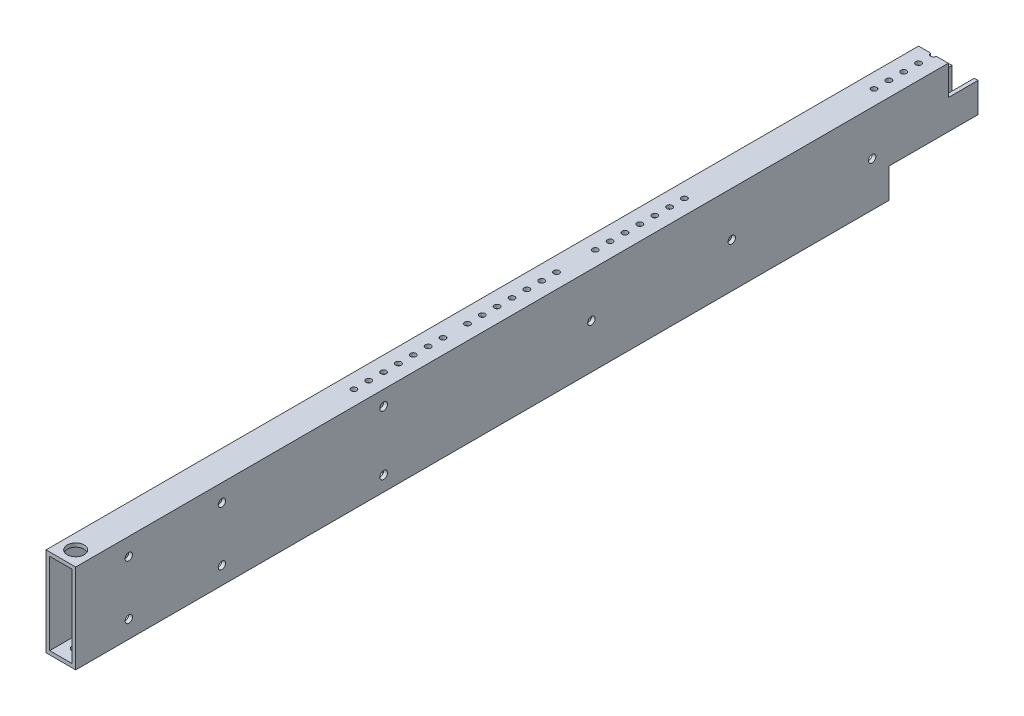
SolidWorks part; units mm, degrees
ref_plane "Front Plane" through (0, 0, 0) normal (0, 0, 1) x (1, 0, 0)
ref_plane "Top Plane" through (0, 0, 0) normal (0, 1, 0) x (1, 0, 0)
ref_plane "Right Plane" through (0, 0, 0) normal (1, 0, 0) x (0, 0, -1)
sketch "Sketch1" plane through (0, 0, 0) normal (0, 0, 1) x (1, 0, 0)
  line L1 (-12.7, -38.1) -> (12.7, -38.1)
  line L2 (-12.7, -38.1) -> (-12.7, 38.1)
  line L3 (-12.7, 38.1) -> (12.7, 38.1)
  line L4 (12.7, -38.1) -> (12.7, 38.1)
  line L5 (-12.7, -38.1) -> (12.7, 38.1) construction
  line L6 (-12.7, 38.1) -> (12.7, -38.1) construction
  point P0 (0, 0)
  dimension "D1" = 25.4
  dimension "D2" = 76.2
extrude "Boss-Extrude1" add sketch "Sketch1" along normal mid plane 771.398
shell "Shell1" thickness 3.175 removed face at (0, 0, -385.699) removed face at (0, 0, 385.699)
sketch "Sketch2" plane through (12.7, 0, 0) normal (1, 0, 0) x (0, 0, -1)
  line L1 (385.699, -38.1) -> (309.499, -38.1)
  line L2 (385.699, -38.1) -> (385.699, -12.7)
  line L3 (385.699, -12.7) -> (309.499, -12.7)
  line L4 (309.499, -38.1) -> (309.499, -12.7)
  dimension "D1" = 25.4
  dimension "D2" = 76.2
extrude "Cut-Extrude1" cut sketch "Sketch2" against normal through all
sketch "Sketch3" plane through (12.7, 0, 0) normal (1, 0, 0) x (0, 0, -1)
  line L1 (385.699, 38.1) -> (360.299, 38.1)
  line L2 (385.699, 38.1) -> (385.699, 12.7)
  line L3 (385.699, 12.7) -> (360.299, 12.7)
  line L4 (360.299, 38.1) -> (360.299, 12.7)
  dimension "D1" = 25.4
extrude "Cut-Extrude2" cut sketch "Sketch3" against normal through all
sketch "Sketch4" plane through (0, 38.1, 0) normal (0, 1, 0) x (1, 0, 0)
  line L0 (-12.7, 360.299) -> (12.7, 360.299) construction
  circle A0 centre (0, 147.3945) radius 2.3812
  circle A1 centre (0, 134.6945) radius 2.3812
  circle A2 centre (0, 121.9945) radius 2.3812
  circle A3 centre (0, 109.2945) radius 2.3812
  circle A4 centre (0, 96.5945) radius 2.3812
  circle A5 centre (0, 83.8945) radius 2.3812
  circle A6 centre (0, 71.1945) radius 2.3812
  circle A7 centre (0, 38.0987) radius 2.3812
  circle A8 centre (0, 25.3987) radius 2.3813
  circle A9 centre (0, 12.6987) radius 2.3813
  circle A10 centre (0, -0.0013) radius 2.3813
  circle A11 centre (0, -12.7013) radius 2.3812
  circle A12 centre (0, -25.4013) radius 2.3812
  circle A13 centre (0, -38.1013) radius 2.3812
  circle A15 centre (0, -58.9932) radius 2.3812
  circle A16 centre (0, -71.6932) radius 2.3812
  circle A17 centre (0, -84.3932) radius 2.3812
  circle A18 centre (0, -97.0932) radius 2.3812
  circle A19 centre (0, -109.7932) radius 2.3812
  circle A20 centre (0, -122.4932) radius 2.3812
  circle A21 centre (0, -135.1932) radius 2.3813
  point P33 (0, 360.299)
  dimension "D1" = 4.7625
  dimension "D3" = 12.7
  dimension "D4" = 12.7
  dimension "D5" = 12.7
  dimension "D6" = 12.7
  dimension "D7" = 12.7
  dimension "D8" = 12.7
  dimension "D9" = 322.2003
  dimension "D10" = 12.7
  dimension "D11" = 12.7
  dimension "D12" = 12.7
  dimension "D13" = 12.7
  dimension "D14" = 12.7
  dimension "D15" = 12.7
  dimension "D16" = 12.7
  dimension "D17" = 419.2922
  dimension "D18" = 12.7
  dimension "D19" = 12.7
  dimension "D20" = 12.7
  dimension "D21" = 12.7
  dimension "D22" = 12.7
  dimension "D2" = 212.9045
extrude "Cut-Extrude3" cut sketch "Sketch4" against normal through all
sketch "Sketch5" plane through (0, 38.1, 0) normal (0, 1, 0) x (1, 0, 0)
  line L0 (-12.7, 360.299) -> (12.7, 360.299) construction
  circle A0 centre (0, 360.299) radius 2.3813
  circle A1 centre (0, 347.599) radius 2.3813
  circle A2 centre (0, 334.899) radius 2.3813
  circle A3 centre (0, 322.199) radius 2.3813
  circle A4 centre (0, 309.499) radius 2.3813
  dimension "D1" = 4.7625
  dimension "D3" = 12.7
  dimension "D4" = 12.7
  dimension "D5" = 12.7
  dimension "D8" = 0
  dimension "D2" = 12.7
extrude "Cut-Extrude4" cut sketch "Sketch5" against normal up to next
sketch "Sketch6" plane through (0, -38.1, 0) normal (0, -1, 0) x (1, 0, 0)
  line L0 (-12.7, -309.499) -> (12.7, -309.499) construction
  circle A0 centre (0, -309.499) radius 2.3813
  circle A1 centre (0, -296.799) radius 2.3813
  circle A2 centre (0, -284.099) radius 2.3813
  circle A3 centre (0, -258.699) radius 2.3813
  circle A6 centre (0, -271.399) radius 2.3813
  dimension "D1" = 4.7625
  dimension "D2" = 12.7
  dimension "D3" = 12.7
  dimension "D4" = 12.7
  dimension "D5" = 12.7
  dimension "D6" = 0
extrude "Cut-Extrude5" cut sketch "Sketch6" against normal up to next
sketch3d "3DSketch1" [suppressed]
  line L0 (0, 34.925, -109.2945) -> (0, 38.1, -109.2945) construction
  line L1 (0, 34.925, 97.0932) -> (0, 38.1, 97.0932) construction
  point P0 (0, 38.1, -109.2945)
  point P1 (0, 0, 0)
  point P4 (0, 38.1, 97.0932)
sketch "Sketch11" plane through (12.7, 0, 0) normal (1, 0, 0) x (0, 0, -1)
  point P0 (-340.3244, 23.1254)
  point P1 (-260.7244, 23.1254)
  point P3 (-260.7244, -23.1)
  point P5 (-340.3244, -23.1)
hole_wizard "CBORE for M6 Hex Head Bolt1" positions "Sketch19" profile "Sketch18" counterbore size "M6" standard "Lanco STD" end condition through all
sketch "Sketch19" plane through (-12.7, 0, 0) normal (-1, 0, 0) x (0, 0, 1)
  point P0 (260.7244, 23.1254)
  point P3 (260.7244, -23.1)
  point P6 (340.3244, 23.1254)
  point P9 (340.3244, -23.1)
sketch "Sketch18" plane through (-12.7, 23.1254, 260.7244) normal (0, 1, 0) x (0, 0, 1)
  line L0 (0, 0) -> (0, 25.4)
  line L1 (0, 25.4) -> (3.15, 25.4)
  line L3 (3.15, 25.4) -> (3.15, 4)
  line L4 (3.15, 4) -> (7.2735, 4)
  line L5 (7.2735, 4) -> (7.2735, 0)
  line L7 (7.2735, 0) -> (0, 0)
  line L11 (0, -6.35) -> (0, 107.95) construction
  dimension "Thru Hole Dia." = 6.3
  dimension "Thru Hole Depth" = 25.4
  dimension "C'Bore Dia." = 14.547
  dimension "C'Bore Depth" = 4
hole_wizard "CBORE for M6 Hex Head Cap Screw1" positions "Sketch21" profile "Sketch20" counterbore size "M6" standard "ANSI Metric" end condition through all
sketch "Sketch21" plane through (-12.7, 0, 0) normal (-1, 0, 0) x (0, 0, 1)
  line L0 (385.699, 38.1) -> (-360.299, 38.1) construction
  line L1 (385.699, 38.1) -> (385.699, -38.1) construction
  point P0 (122.4678, 25.4)
  point P2 (122.4678, -25.4)
  dimension "D1" = 12.7
  dimension "D2" = 63.5
  dimension "D3" = 263.2312
  dimension "D4" = 263.2312
sketch "Sketch20" plane through (-12.7, 25.4, 122.4678) normal (0, 1, 0) x (0, 0, 1)
  line L0 (0, 0) -> (0, 25.4)
  line L1 (0, 25.4) -> (3.3, 25.4)
  line L3 (3.3, 25.4) -> (3.3, 4.15)
  line L4 (3.3, 4.15) -> (7.275, 4.15)
  line L5 (7.275, 4.15) -> (7.275, 0)
  line L7 (7.275, 0) -> (0, 0)
  line L11 (0, -6.35) -> (0, 107.95) construction
  dimension "Thru Hole Dia." = 6.6
  dimension "Thru Hole Depth" = 25.4
  dimension "C'Bore Dia." = 14.55
  dimension "C'Bore Depth" = 4.15
hole_wizard "CBORE for M6 Hex Head Cap Screw2" positions "Sketch26" profile "Sketch25" counterbore size "M6" standard "ANSI Metric" end condition through all
sketch "Sketch26" plane through (0, 38.1, 0) normal (0, 1, 0) x (1, 0, 0)
  line L0 (12.7, -385.699) -> (-12.7, -385.699) construction
  point P0 (0, -372.999)
  dimension "D1" = 12.7
sketch "Sketch25" plane through (0, 38.1, 372.999) normal (1, 0, 0) x (0, 0, 1)
  line L0 (0, 0) -> (0, 76.2)
  line L1 (0, 76.2) -> (3.3, 76.2)
  line L3 (3.3, 76.2) -> (3.3, 4.15)
  line L4 (3.3, 4.15) -> (7.275, 4.15)
  line L5 (7.275, 4.15) -> (7.275, 0)
  line L7 (7.275, 0) -> (0, 0)
  line L11 (0, -6.35) -> (0, 107.95) construction
  dimension "Thru Hole Dia." = 6.6
  dimension "Thru Hole Depth" = 76.2
  dimension "C'Bore Dia." = 14.55
  dimension "C'Bore Depth" = 4.15
hole_wizard "Ø6.4 (6.4) Diameter Hole1" positions "Sketch28" profile "Sketch27" hole size "Ø6.4" standard "ANSI Metric" end condition through all
sketch "Sketch28" plane through (12.7, 0, 0) normal (1, 0, 0) x (0, 0, -1)
  point P0 (55.1949, 0)
  point P3 (175.1949, 0)
  point P6 (295.1949, 0)
sketch "Sketch27" plane through (12.7, 0, -55.1949) normal (0, 1, 0) x (0, 0, -1)
  line L0 (0, 0) -> (0, 25.4)
  line L1 (0, 25.4) -> (3.2, 25.4)
  line L2 (3.2, 25.4) -> (3.2, 0)
  line L5 (3.2, 0) -> (0, 0)
  line L11 (0, -6.35) -> (0, 107.95) construction
  dimension "Thru Hole Dia." = 6.4
  dimension "Thru Hole Depth" = 25.4
